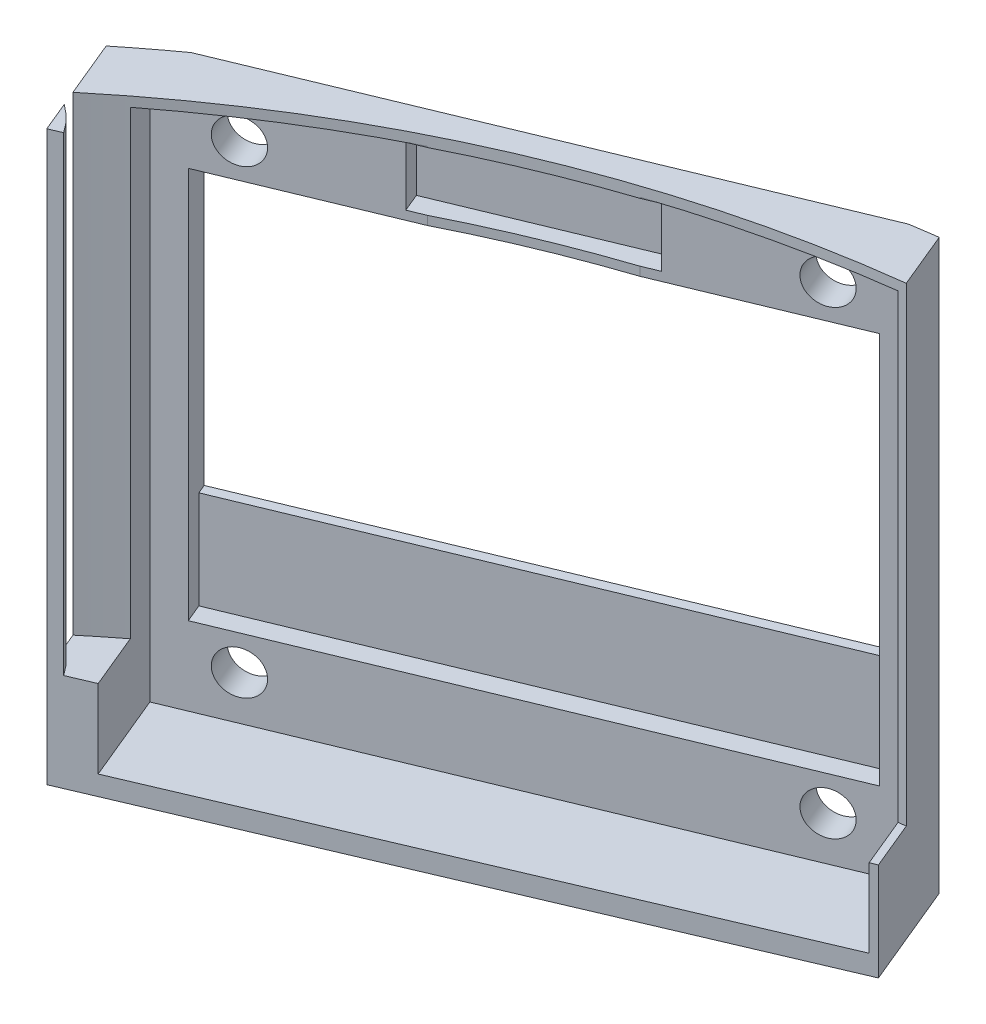
SolidWorks part; units mm, degrees
ref_plane "Front Plane" through (0, 0, 0) normal (0, 0, 1) x (1, 0, 0)
ref_plane "Top Plane" through (0, 0, 0) normal (0, 1, 0) x (1, 0, 0)
ref_plane "Right Plane" through (0, 0, 0) normal (1, 0, 0) x (0, 0, -1)
sketch "Sketch1" plane through (0, 0, 0) normal (0, 1, 0) x (1, 0, 0)
  circle A0 centre (0, 0) radius 60.325
  dimension "D1" = 120.65
extrude "Boss-Extrude1" add sketch "Sketch1" along normal blind 5
sketch "Sketch2" plane through (0, 5, 0) normal (0, 1, 0) x (1, 0, 0)
  line L9 (-15, -10) -> (15, -10)
  line L10 (-15, -10) -> (-15, 30)
  line L11 (-15, 30) -> (15, 30)
  line L12 (15, -10) -> (15, 30)
  line L13 (-15, -10) -> (15, 30) construction
  line L14 (-15, 30) -> (15, -10) construction
  point P0 (0.3114, 20.4789)
  point P5 (0, 10)
  dimension "D1" = 30
  dimension "D2" = 40
  dimension "D3" = 10
  dimension "D4" = 0
extrude "Boss-Extrude2" [suppressed] add sketch "Sketch2" along normal blind 20
sketch "Sketch3" plane through (0, 5, 0) normal (0, 1, 0) x (1, 0, 0)
  circle A0 centre (0, 0) radius 60.325
  circle A1 centre (0, 0) radius 57.325
  dimension "D1" = 114.65
  dimension "D2" = 3
extrude "Boss-Extrude3" add sketch "Sketch3" along normal blind 24
sketch "Sketch5" plane through (0, 5, 0) normal (0, 1, 0) x (1, 0, 0)
  line L0 (0, 0) -> (-39.2444, 39.2444)
  line L1 (0, 0) -> (39.2444, 39.2444)
  line L2 (0, 0) -> (-39.2444, -39.2444)
  line L3 (0, 0) -> (39.2444, -39.2444)
  circle A0 centre (-39.2444, 39.2444) radius 2
  circle A1 centre (-39.2444, 39.2444) radius 5
  circle A2 centre (39.2444, 39.2444) radius 2
  circle A3 centre (39.2444, 39.2444) radius 5
  circle A4 centre (-39.2444, -39.2444) radius 2
  circle A5 centre (-39.2444, -39.2444) radius 5
  circle A6 centre (39.2444, -39.2444) radius 2
  circle A7 centre (39.2444, -39.2444) radius 5
  circle A8 centre (0, 0) radius 60.325 construction
  circle M19 centre (0, 0) radius 57.325
  dimension "D1" = 4
  dimension "D2" = 10
  dimension "D3" = 4
  dimension "D4" = 10
  dimension "D5" = 10
  dimension "D6" = 4
  dimension "D7" = 4
  dimension "D8" = 10
  dimension "D9" = 55.5
  dimension "D10" = 55.5
  dimension "D11" = 55.5
  dimension "D12" = 55.5
ref_plane "Plane1" through (0, 0, 60.325) normal (0, 0, 1) x (1, 0, 0)
sketch "Sketch6" plane through (0, 0, 60.325) normal (0, 0, 1) x (1, 0, 0)
  line L1 (-7.5, 19.5) -> (7.5, 19.5)
  line L2 (-7.5, 19.5) -> (-7.5, 4.5)
  line L3 (-7.5, 4.5) -> (7.5, 4.5)
  line L4 (7.5, 19.5) -> (7.5, 4.5)
  line L5 (-7.5, 19.5) -> (7.5, 4.5) construction
  line L6 (-7.5, 4.5) -> (7.5, 19.5) construction
  point P0 (0, 12)
  dimension "D1" = 12
  dimension "D2" = 15
  dimension "D3" = 15
extrude "Boss-Extrude13" add sketch "Sketch6" against normal blind 2
sketch "Sketch7" plane through (0, 0, 60.325) normal (0, 0, 1) x (1, 0, 0)
  circle A0 centre (0, 12.3134) radius 5.5
  dimension "D1" = 11
extrude "Cut-Extrude1" cut sketch "Sketch7" against normal blind 5
sketch "Sketch8" [suppressed] plane through (0, 0, 10) normal (0, 0, 1) x (1, 0, 0)
  line L0 (-15, 5) -> (15, 5) construction
  line L1 (-12.0184, 27.5) -> (12.0184, 27.5)
  line L2 (-12.0184, 27.5) -> (-12.0184, 7.5)
  line L3 (-12.0184, 7.5) -> (12.0184, 7.5)
  line L4 (12.0184, 27.5) -> (12.0184, 7.5)
  line L5 (-12.0184, 27.5) -> (12.0184, 7.5) construction
  line L6 (-12.0184, 7.5) -> (12.0184, 27.5) construction
  point P0 (0, 17.5)
  dimension "D1" = 12.5
  dimension "D2" = 20
extrude "Cut-Extrude2" [suppressed] cut sketch "Sketch8" against normal blind 50
sketch "Sketch11" [suppressed] plane through (-15, 0, 0) normal (-1, 0, 0) x (0, 0, 1)
  line L0 (-30, 5) -> (10, 5) construction
  line L1 (-30, 25) -> (-30, 5) construction
  circle A0 centre (-15, 15) radius 2
  circle A1 centre (4, 15) radius 2
  dimension "D2" = 4
  dimension "D3" = 4
  dimension "D1" = 19
  dimension "D4" = 10
  dimension "D5" = 15
extrude "Cut-Extrude5" [suppressed] cut sketch "Sketch11" against normal blind 20
sketch "Sketch12" [suppressed] plane through (15, 0, 0) normal (1, 0, 0) x (0, 0, -1)
  line L0 (-10, 25) -> (-10, 5) construction
  line L1 (-10, 5) -> (30, 5) construction
  circle A0 centre (3, 15) radius 2
  circle A1 centre (26, 15) radius 2
  dimension "D3" = 4
  dimension "D4" = 4
  dimension "D1" = 23
  dimension "D2" = 13
  dimension "D5" = 10
extrude "Cut-Extrude6" [suppressed] cut sketch "Sketch12" against normal blind 20
ref_plane "Plane2" through (0, 0, -60.325) normal (0, 0, -1) x (-1, 0, 0)
sketch "Sketch14" plane through (0, 0, -60.325) normal (0, 0, -1) x (-1, 0, 0)
  circle A0 centre (0, 13.2159) radius 2.5
  dimension "D1" = 5
extrude "Cut-Extrude7" cut sketch "Sketch14" against normal blind 5
ref_plane "Plane3" through (-60.325, 0, 0) normal (-1, 0, 0) x (0, 0, 1)
sketch "Sketch15" plane through (-60.325, 0, 0) normal (-1, 0, 0) x (0, 0, 1)
  circle A1 centre (0, 14.0795) radius 12.5
  dimension "D1" = 25
extrude "Boss-Extrude15" add sketch "Sketch15" against normal blind 3
sketch "Sketch16" plane through (-60.325, 0, 0) normal (-1, 0, 0) x (0, 0, 1)
  circle A0 centre (0, 14.3674) radius 10.5
  dimension "D1" = 21
extrude "Cut-Extrude9" cut sketch "Sketch16" against normal blind 5
sketch "Sketch17" plane through (0, 5, 0) normal (0, 1, 0) x (1, 0, 0)
  circle A0 centre (0, 40) radius 2.5
  circle A1 centre (40, 0) radius 2.5
  circle A2 centre (0, -40) radius 2.5
  circle A3 centre (-40, 0) radius 2.5
  dimension "D5" = 5
  dimension "D6" = 5
  dimension "D7" = 5
  dimension "D8" = 5
  dimension "D1" = 40
  dimension "D2" = 40
  dimension "D3" = 40
  dimension "D4" = 40
extrude "Cut-Extrude10" cut sketch "Sketch17" against normal blind 5
ref_plane "Plane4" through (60.325, 0, 0) normal (1, 0, 0) x (0, 0, -1)
sketch "Sketch20" plane through (0, 5, 0) normal (0, 1, 0) x (1, 0, 0)
  line L1 (-5.1053, 49.3333) -> (5.5119, 49.3333)
  line L2 (-5.1053, 49.3333) -> (-5.1053, 44.4903)
  line L3 (-5.1053, 44.4903) -> (5.5119, 44.4903)
  line L4 (5.5119, 49.3333) -> (5.5119, 44.4903)
  line L5 (-5.1053, 49.3333) -> (5.5119, 44.4903) construction
  line L6 (-5.1053, 44.4903) -> (5.5119, 49.3333) construction
  point P0 (0.2033, 46.9118)
extrude "Cut-Extrude13" cut sketch "Sketch20" against normal blind 1
ref_plane "Plane6" through (50, 0, 0) normal (1, 0, 0) x (0, 0, -1)
sketch "Sketch26" plane through (50, 0, 0) normal (1, 0, 0) x (0, 0, -1)
  line L1 (-25, 5) -> (25, 5)
  line L2 (-25, 5) -> (-25, 29)
  line L3 (-25, 29) -> (25, 29)
  line L4 (25, 5) -> (25, 29)
  line L5 (-25, 5) -> (25, 29) construction
  line L6 (-25, 29) -> (25, 5) construction
  point P0 (0, 17)
  dimension "D1" = 0
  dimension "D2" = 17
  dimension "D3" = 24
  dimension "D4" = 50
extrude "Boss-Extrude46" add sketch "Sketch26" along normal blind 10
sketch "Sketch27" plane through (60.325, 0, 0) normal (1, 0, 0) x (0, 0, -1)
  line L1 (-22.5, 5) -> (22.5, 5)
  line L2 (-22.5, 5) -> (-22.5, 25)
  line L3 (-22.5, 25) -> (22.5, 25)
  line L4 (22.5, 5) -> (22.5, 25)
  line L5 (-22.5, 5) -> (22.5, 25) construction
  line L6 (-22.5, 25) -> (22.5, 5) construction
  point P0 (0, 15)
  dimension "D1" = 45
  dimension "D2" = 20
  dimension "D3" = 0
  dimension "D4" = 15
extrude "Cut-Extrude15" cut sketch "Sketch27" against normal blind 5
sketch "Sketch28" plane through (60.325, 0, 0) normal (1, 0, 0) x (0, 0, -1)
  line L1 (-17.5, 23.3481) -> (17.5, 23.3481)
  line L2 (-17.5, 23.3481) -> (-17.5, 6.6519)
  line L3 (-17.5, 6.6519) -> (17.5, 6.6519)
  line L4 (17.5, 23.3481) -> (17.5, 6.6519)
  line L5 (-17.5, 23.3481) -> (17.5, 6.6519) construction
  line L6 (-17.5, 6.6519) -> (17.5, 23.3481) construction
  point P0 (0, 15)
  dimension "D1" = 35
  dimension "D2" = 15
  dimension "D3" = 0
sketch "Sketch29" plane through (55.325, 0, 0) normal (1, 0, 0) x (0, 0, -1)
  circle A0 centre (-20, 21) radius 1.1
  circle A1 centre (-20, 9) radius 1.1
  circle A2 centre (20, 21) radius 1.1
  circle A3 centre (20, 9.1519) radius 1.1
  dimension "D1" = 2.2
  dimension "D2" = 2.2
  dimension "D3" = 2.2
  dimension "D4" = 2.2
  dimension "D5" = 40
  dimension "D6" = 12
  dimension "D7" = 9
extrude "Cut-Extrude17" cut sketch "Sketch29" against normal blind 10
extrude "Cut-Extrude18" cut sketch "Sketch28" against normal blind 20
sketch "Sketch30" plane through (0, 29, 0) normal (0, 1, 0) x (1, 0, 0)
  line L0 (51.7831, 30.9453) -> (68.4097, 30.9453)
  line L1 (50.8846, -32.4016) -> (67.7321, -32.4016)
  arc A0 (50.8846, -32.4016) -> (51.7831, 30.9453) centre (0, 0) ccw
  arc A1 (67.7321, -32.4016) -> (68.4097, 30.9453) centre (0, 0) ccw
  dimension "D1" = 120.65
extrude "Boss-Extrude47" add sketch "Sketch5" along normal blind 24 contours L0 A1 A0 M19 | A1 L0 A0 M19 | A5 L2 A4 M19 | L2 A5 A4 M19 | A7 L3 A6 M19 | L3 A7 A6 M19 | L1 A3 A2 M19 | A3 L1 A2 M19 region at (-39.9858, 5, -36.3261) region at (-36.3261, 5, -39.9858) region at (36.3261, 5, -39.9858) region at (39.9858, 5, -36.3261) region at (-36.3261, 5, 39.9858) region at (-39.9858, 5, 36.3261) region at (39.9858, 5, 36.3261) region at (36.3261, 5, 39.9858)
extrude "Cut-Extrude19" cut sketch "Sketch30" against normal blind 30
sketch "Sketch31" plane through (0, 5, 0) normal (0, 1, 0) x (1, 0, 0)
  circle A0 centre (-33.05, 28) radius 3
  circle A1 centre (-14, 28) radius 3
  circle A2 centre (-14, -27.88) radius 3
  circle A3 centre (-33.05, -27.88) radius 3
  point P8 (-31.4059, 23.5)
  point P10 (-33.0174, -32.3568)
  point P11 (0, 0)
  point P12 (0, 0)
  point P13 (-29.4216, 21.25)
  dimension "D9" = 6
  dimension "D10" = 6
  dimension "D11" = 6
  dimension "D12" = 6
  dimension "D2" = 55.88
  dimension "D3" = 14
  dimension "D4" = 14
  dimension "D5" = 19.05
  dimension "D6" = 28
  dimension "D7" = 55.88
  dimension "D8" = 0
  dimension "D13" = 19.05
extrude "Boss-Extrude48" add sketch "Sketch31" along normal blind 10
sketch "Sketch32" plane through (0, 15, 0) normal (0, 1, 0) x (1, 0, 0)
  circle A0 centre (-14, -27.88) radius 1.5
  circle A1 centre (-33.05, -27.88) radius 1.5
  circle A2 centre (-33.05, 28) radius 1.5
  circle A3 centre (-14, 28) radius 1.5
  dimension "D1" = 3
  dimension "D2" = 3
  dimension "D3" = 3
  dimension "D4" = 3
extrude "Cut-Extrude20" cut sketch "Sketch32" against normal blind 5
sketch "Sketch33" plane through (0, 5, 0) normal (0, 1, 0) x (1, 0, 0)
  line L9 (-6.75, -14.6471) -> (-3.25, -14.6471)
  line L10 (-6.75, -14.6471) -> (-6.75, -9.3529)
  line L11 (-6.75, -9.3529) -> (-3.25, -9.3529)
  line L12 (-3.25, -14.6471) -> (-3.25, -9.3529)
  line L13 (-6.75, -14.6471) -> (-3.25, -9.3529) construction
  line L14 (-6.75, -9.3529) -> (-3.25, -14.6471) construction
  line L15 (4.65, -14.6471) -> (8.15, -14.6471)
  line L16 (4.65, -14.6471) -> (4.65, -9.3529)
  line L17 (4.65, -9.3529) -> (8.15, -9.3529)
  line L18 (8.15, -14.6471) -> (8.15, -9.3529)
  line L19 (4.65, -14.6471) -> (8.15, -9.3529) construction
  line L20 (4.65, -9.3529) -> (8.15, -14.6471) construction
  circle A0 centre (-5, 35) radius 2.5
  circle A1 centre (6.4, 35.005) radius 2.5
  point P12 (-5, -12)
  point P17 (6.4, -12)
  dimension "D1" = 5
  dimension "D2" = 5
  dimension "D3" = 11.4
  dimension "D4" = 11.4
  dimension "D5" = 47
  dimension "D6" = 12
  dimension "D7" = 5
  dimension "D8" = 3.5
  dimension "D9" = 3.5
  dimension "D10" = 5
extrude "Boss-Extrude49" add sketch "Sketch33" along normal blind 5
sketch "Sketch34" plane through (0, 10, 0) normal (0, 1, 0) x (1, 0, 0)
  circle A1 centre (6.4, 35.005) radius 1.1
  circle A2 centre (6.4, -12) radius 1.1
  circle A3 centre (-5, -12) radius 1.1
  circle A4 centre (-5, 35) radius 1.1
  dimension "D1" = 2.2
  dimension "D2" = 2.2
  dimension "D3" = 2.2
  dimension "D4" = 2.2
  dimension "D5" = 12
  dimension "D6" = 12
extrude "Cut-Extrude21" cut sketch "Sketch34" against normal blind 5
sketch "Sketch35" plane through (0, 5, 0) normal (0, 1, 0) x (1, 0, 0)
  line L1 (14, 20) -> (17, 20)
  line L2 (14, 20) -> (14, -20)
  line L3 (14, -20) -> (17, -20)
  line L4 (17, 20) -> (17, -20)
  dimension "D1" = 17
  dimension "D2" = 3
  dimension "D3" = 40
  dimension "D4" = 20
extrude "Boss-Extrude50" add sketch "Sketch35" along normal blind 15
ref_axis "Axis1" through (0, 28.35, 0) along (0, -1, 0)
ref_plane "Plane8" through (-23.0854, 0, 55.733) normal (-0.3827, 0, 0.9239) x (0, -1, 0)
ref_plane "Plane9" through (0, 0, 0) normal (0.9239, 0, 0.3827) x (0, -1, 0)
ref_plane "Plane10" through (23.0854, 0, 55.733) normal (0.3827, 0, 0.9239) x (0, -1, 0)
ref_plane "Plane11" through (21.172, 0, 51.1136) normal (0.3827, 0, 0.9239) x (0, -1, 0)
sketch "Sketch39" plane through (21.172, 0, 51.1136) normal (0.3827, 0, 0.9239) x (0, -1, 0)
  line L1 (-29, 15.0144) -> (-5, 15.0144)
  line L2 (-29, 15.0144) -> (-29, -14.9856)
  line L3 (-29, -14.9856) -> (-5, -14.9856)
  line L4 (-5, 15.0144) -> (-5, -14.9856)
  dimension "D1" = 24
  dimension "D2" = 5
  dimension "D3" = 30
extrude "Boss-Extrude51" add sketch "Sketch39" along normal blind 2
sketch "Sketch37" plane through (23.0854, 0, 55.733) normal (0.3827, 0, 0.9239) x (0, -1, 0)
  line L1 (-25, 14) -> (-5, 14)
  line L2 (-25, 14) -> (-25, -14)
  line L3 (-25, -14) -> (-5, -14)
  line L4 (-5, 14) -> (-5, -14)
  dimension "D1" = 20
  dimension "D2" = 5
  dimension "D3" = 28
  dimension "D4" = 14
extrude "Cut-Extrude25" cut sketch "Sketch37" against normal blind 2
sketch "Sketch40" plane through (23.0854, 0, 55.733) normal (0.3827, 0, 0.9239) x (0, -1, 0)
  line L1 (-23, 10) -> (-7, 10)
  line L2 (-23, 10) -> (-23, -10)
  line L3 (-23, -10) -> (-7, -10)
  line L4 (-7, 10) -> (-7, -10)
  dimension "D1" = 16
  dimension "D2" = 7
  dimension "D3" = 10
  dimension "D4" = 20
extrude "Cut-Extrude26" cut sketch "Sketch40" against normal blind 12
sketch "Sketch41" plane through (23.0854, 0, 55.733) normal (0.3827, 0, 0.9239) x (0, -1, 0)
  circle A0 centre (-21, 12) radius 1.1
  circle A1 centre (-9, 12) radius 1.1
  circle A2 centre (-9, -12) radius 1.1
  circle A3 centre (-21, -12) radius 1.1
  dimension "D5" = 2.2
  dimension "D6" = 2.2
  dimension "D7" = 2.2
  dimension "D8" = 2.2
  dimension "D1" = 12
  dimension "D2" = 9
  dimension "D3" = 12
  dimension "D4" = 9
  dimension "D9" = 24
  dimension "D10" = 24
  dimension "D11" = 12
  dimension "D12" = 12
extrude "Cut-Extrude27" cut sketch "Sketch41" against normal blind 12
mirror "Mirror2" about plane through (0, 0, 0) normal (1, 0, 0) of "Boss-Extrude51", "Cut-Extrude25", "Cut-Extrude26", "Cut-Extrude27"
ref_plane "Plane12" through (-20.9232, 0, -50.5131) normal (0.3827, 0, 0.9239) x (0, -1, 0)
sketch "Sketch43" plane through (-20.9232, 0, -50.5131) normal (0.3827, 0, 0.9239) x (0, -1, 0)
  line L1 (-28.5, 15) -> (-1, 15)
  line L2 (-28.5, 15) -> (-28.5, -15)
  line L3 (-28.5, -15) -> (-1, -15)
  line L4 (-1, 15) -> (-1, -15)
  dimension "D1" = 30
  dimension "D2" = 27.5
  dimension "D3" = 1
  dimension "D4" = 15
extrude "Cut-Extrude28" cut sketch "Sketch43" against normal blind 2.5 and the other way blind 4
sketch "Sketch44" plane through (0, 5, 0) normal (0, 1, 0) x (1, 0, 0)
  circle A0 centre (-20, 45) radius 2.5
  circle A2 centre (18.2295, 45) radius 2.5
  circle A3 centre (18.2295, -32.0272) radius 2.5
  dimension "D3" = 5
  dimension "D4" = 5
  dimension "D5" = 5
  dimension "D1" = 20
  dimension "D2" = 45
extrude "Boss-Extrude52" add sketch "Sketch44" along normal blind 5
sketch "Sketch45" plane through (0, 10, 0) normal (0, 1, 0) x (1, 0, 0)
  circle A0 centre (-20, 45) radius 1.1
  circle A1 centre (18.2295, 45) radius 1.1
  circle A2 centre (18.2295, -32.0272) radius 1.1
  dimension "D1" = 2.2
  dimension "D2" = 2.2
  dimension "D3" = 2.2
extrude "Cut-Extrude29" cut sketch "Sketch45" against normal blind 5
sketch "Sketch46" plane through (-21.8799, 0, -52.8228) normal (0.3827, 0, 0.9239) x (0.9239, 0, -0.3827)
  line L1 (-13.5, 25) -> (13.5, 25)
  line L2 (-13.5, 25) -> (-13.5, 10)
  line L3 (-13.5, 10) -> (13.5, 10)
  line L4 (13.5, 25) -> (13.5, 10)
  dimension "D1" = 27
  dimension "D2" = 15
  dimension "D3" = 10
  dimension "D4" = 13.5
extrude "Cut-Extrude30" cut sketch "Sketch46" against normal blind 5
sketch "Sketch47" plane through (-21.8799, 0, -52.8228) normal (0.3827, 0, 0.9239) x (0.9239, 0, -0.3827)
  circle A0 centre (11.5, 26.75) radius 1.1
  circle A1 centre (-11.5, 26.75) radius 1.1
  circle A2 centre (-11.5, 3.25) radius 1.1
  circle A3 centre (11.5, 3.25) radius 1.1
  dimension "D4" = 2.2
  dimension "D5" = 2.2
  dimension "D6" = 2.2
  dimension "D7" = 2.2
  dimension "D1" = 23
  dimension "D2" = 23.5
  dimension "D3" = 23
  dimension "D8" = 3.25
  dimension "D9" = 11.5
extrude "Cut-Extrude31" cut sketch "Sketch47" against normal blind 3
ref_plane "Plane13" through (-22.454, 0, -54.2086) normal (0.3827, 0, 0.9239) x (0, -1, 0)
sketch "Sketch48" plane through (-22.454, 0, -54.2086) normal (0.3827, 0, 0.9239) x (0, -1, 0)
  line L1 (-35, 15) -> (5, 15)
  line L2 (-35, 15) -> (-35, -15)
  line L3 (-35, -15) -> (5, -15)
  line L4 (5, 15) -> (5, -15)
  dimension "D1" = 30
  dimension "D2" = 15
  dimension "D3" = 5
  dimension "D4" = 40
extrude "Cut-Extrude32" cut sketch "Sketch48" against normal blind 5
sketch "Sketch49" plane through (-21.8799, 0, -52.8228) normal (0.3827, 0, 0.9239) x (0.9239, 0, -0.3827)
  line L1 (-5, 28.45) -> (5, 28.45)
  line L2 (-5, 28.45) -> (-5, 25.45)
  line L3 (-5, 25.45) -> (5, 25.45)
  line L4 (5, 28.45) -> (5, 25.45)
  line L5 (-13.5, 10) -> (13.5, 10)
  line L6 (-13.5, 10) -> (-13.5, 5)
  line L7 (-13.5, 5) -> (13.5, 5)
  line L8 (13.5, 10) -> (13.5, 5)
  dimension "D1" = 10
  dimension "D2" = 3
  dimension "D3" = 5
  dimension "D4" = 27
  dimension "D5" = 13.5
  dimension "D6" = 5
  dimension "D7" = 5
extrude "Cut-Extrude33" cut sketch "Sketch49" against normal blind 1
sketch "Sketch50" plane through (-22.454, 0, -54.2086) normal (0.3827, 0, 0.9239) x (0, -1, 0)
  line L1 (-45.0003, 15.3623) -> (9.2858, 15.3623)
  line L2 (-45.0003, 15.3623) -> (-45.0003, 92.5058)
  line L3 (-45.0003, 92.5058) -> (9.2858, 92.5058)
  line L4 (9.2858, 15.3623) -> (9.2858, 92.5058)
  line L5 (-45.0003, -17) -> (9.2858, -17)
  line L6 (-45.0003, -17) -> (-45.0003, -76.7148)
  line L7 (-45.0003, -76.7148) -> (9.2858, -76.7148)
  line L8 (9.2858, -17) -> (9.2858, -76.7148)
  dimension "D1" = 17
extrude "Cut-Extrude34" cut sketch "Sketch50" along normal blind 122
sketch "Sketch51" plane through (0, 5, 0) normal (0, 1, 0) x (1, 0, 0)
  line L0 (-45.3732, 37.6789) -> (7.9734, 60.4006)
  line L1 (7.9734, 60.4006) -> (56.6196, -53.8122)
  line L2 (56.6196, -53.8122) -> (1.6861, -72.8082)
  line L3 (1.6861, -72.8082) -> (-45.3732, 37.6789)
extrude "Cut-Extrude35" cut sketch "Sketch51" against normal blind 122 and the other way blind 122
